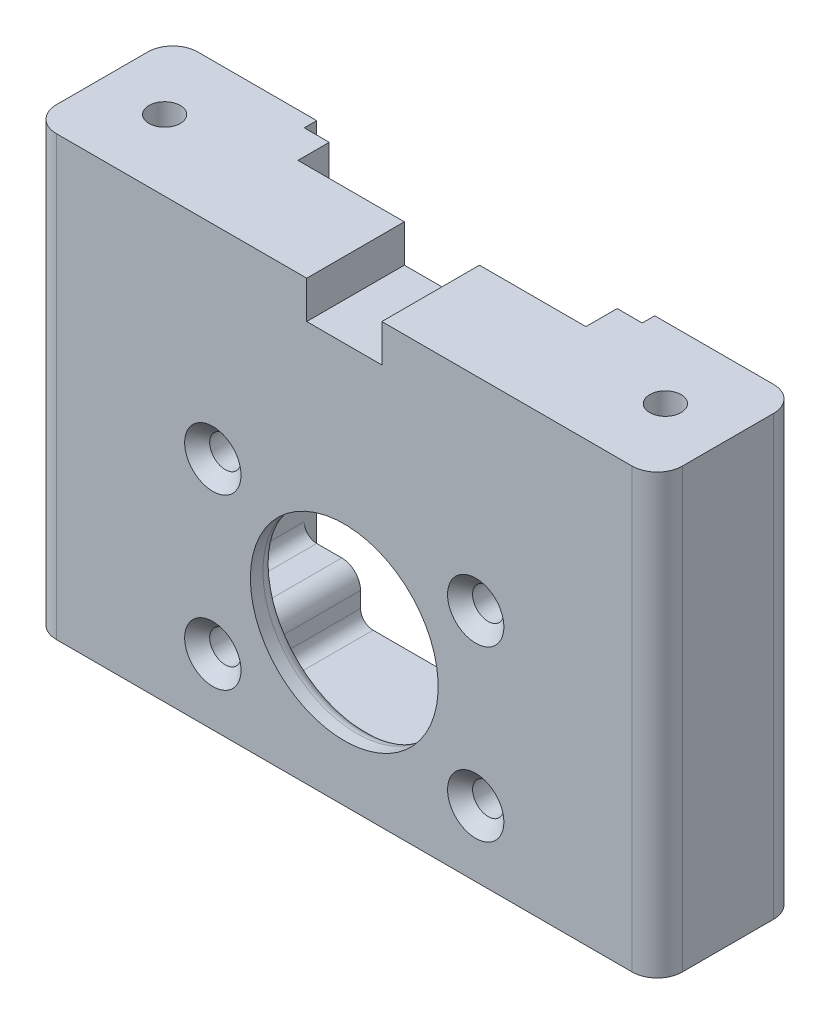
SolidWorks part; units mm, degrees
ref_plane "Спереди" through (0, 0, 0) normal (0, 0, 1) x (1, 0, 0)
ref_plane "Сверху" through (0, 0, 0) normal (0, 1, 0) x (1, 0, 0)
ref_plane "Справа" through (0, 0, 0) normal (1, 0, 0) x (0, 0, -1)
sketch "Эскиз1" plane through (0, 0, 0) normal (0, 0, 1) x (1, 0, 0)
  line L0 (0, 23) -> (0, -12) construction
  line L1 (-25, 23) -> (25, 23)
  line L2 (-25, 23) -> (-25, -12)
  line L3 (-25, -12) -> (25, -12)
  line L4 (25, 23) -> (25, -12)
  line L5 (-25, 0) -> (25, 0) construction
  point P4 (0, 0)
  dimension "D1" = 12
  dimension "D2" = 23
  dimension "D3" = 50
extrude "тело" add sketch "Эскиз1" along normal blind 11.3
sketch "Эскиз2" plane through (0, 0, 0) normal (0, 0, -1) x (-1, 0, 0)
  line L0 (0, 6.75) -> (0, -6.75) construction
  line L1 (-10.5, 6.75) -> (10.5, 6.75) construction
  line L2 (-10.5, 6.75) -> (-10.5, -6.75) construction
  line L3 (-10.5, -6.75) -> (10.5, -6.75) construction
  line L4 (10.5, 6.75) -> (10.5, -6.75) construction
  line L6 (-10.5, 0) -> (10.5, 0) construction
  circle A0 centre (0, 0) radius 7.5
  circle A1 centre (-10.5, 6.75) radius 1.25
  circle A2 centre (10.5, 6.75) radius 1.25
  circle A3 centre (10.5, -6.75) radius 1.25
  circle A4 centre (-10.5, -6.75) radius 1.25
  point P15 (0, 0)
  dimension "D1" = 2.5
  dimension "D4" = 15
  dimension "D2" = 21
  dimension "D3" = 13.5
extrude "отверстия под объектив и крепления" cut sketch "Эскиз2" against normal through all
sketch "Эскиз3" plane through (0, 0, 0) normal (0, 0, -1) x (-1, 0, 0)
  line L1 (-13.5, 10.25) -> (13.5, 10.25)
  line L2 (-13.5, 10.25) -> (-13.5, 8.25)
  line L3 (-9, -9) -> (9, -9)
  line L4 (13.5, 10.25) -> (13.5, 8.25)
  line L5 (-10.5, 8.25) -> (-13.5, 8.25)
  line L6 (-10.5, 5.25) -> (-13.5, 5.25)
  line L7 (10.5, 8.25) -> (13.5, 8.25)
  line L8 (10.5, -5.25) -> (13.5, -5.25)
  line L9 (10.5, 5.25) -> (13.5, 5.25)
  line L10 (-10.5, -5.25) -> (-13.5, -5.25)
  line L11 (-9, -6.75) -> (-9, -9)
  line L12 (-13.5, 5.25) -> (-13.5, -5.25)
  line L13 (9, -6.75) -> (9, -9)
  line L16 (13.5, 5.25) -> (13.5, -5.25)
  arc A0 (-10.5, 5.25) -> (-10.5, 8.25) centre (-10.5, 6.75) ccw
  arc A1 (-9, -6.75) -> (-10.5, -5.25) centre (-10.5, -6.75) ccw
  arc A2 (10.5, 8.25) -> (10.5, 5.25) centre (10.5, 6.75) ccw
  arc A3 (10.5, -5.25) -> (9, -6.75) centre (10.5, -6.75) ccw
  dimension "D2" = 3
  dimension "D1" = 9
  dimension "D3" = 10.25
  dimension "D4" = 13.5
extrude "углубление под выступы камеры" cut sketch "Эскиз3" against normal blind 9.3
sketch "Эскиз4" plane through (0, 0, 0) normal (0, 0, -1) x (-1, 0, 0)
  line L0 (-13.5, 0) -> (13.5, 0) construction
  line L1 (-13.5, 23) -> (13.5, 23)
  line L2 (-13.5, 23) -> (-13.5, -11.5)
  line L3 (-13.5, -11.5) -> (13.5, -11.5)
  line L4 (13.5, 23) -> (13.5, -11.5)
  line L6 (-25, 23) -> (25, 23) construction
  point P6 (0, 0)
  dimension "D1" = 27
  dimension "D2" = 11.5
extrude "углубление под плату камеры" cut sketch "Эскиз4" against normal blind 1
sketch "Эскиз5" plane through (0, 23, 0) normal (0, 1, 0) x (1, 0, 0)
  line L0 (0, 0) -> (0, -11.3) construction
  line L1 (25, -11.3) -> (-25, -11.3) construction
  line L2 (25, 0) -> (13.5, 0) construction
  line L3 (-11.5, 0) -> (11.5, 0)
  line L4 (-11.5, 0) -> (-11.5, -3.5)
  line L5 (-11.5, -3.5) -> (11.5, -3.5)
  line L6 (11.5, 0) -> (11.5, -3.5)
  point P12 (0, 0)
  dimension "D1" = 23
  dimension "D2" = 3.5
extrude "вырез под шлейф" cut sketch "Эскиз5" against normal up to surface (12.75 mm away) up to face at (0, 10.25, 5.15)
fillet "Скругление1" radius 1 2 edges at (0, 10.25, 3.5) (-7.5, 0, 9.3)
fillet "Скругление3" radius 1 26 edges at (-12, 8.25, 9.3) (12, 8.25, 9.3) (13.5, 8.25, 5.15) (13.5, 9.25, 9.3) (0, 10.25, 9.3) (-13.5, 9.25, 9.3) (-13.5, 8.25, 5.15) (-9, 6.75, 9.3) (-12, 5.25, 9.3) (-13.5, 5.25, 5.15) (-13.5, 0, 9.3) (-13.5, -5.25, 5.15) (-12, -5.25, 9.3) (-9.4393, -5.6893, 9.3) (-9, -7.875, 9.3) (-9, -9, 5.15) (0, -9, 9.3) (9, -9, 5.15) (9, -7.875, 9.3) (9.4393, -5.6893, 9.3) (12, -5.25, 9.3) (13.5, -5.25, 5.15) (13.5, 0, 9.3) (12, 5.25, 9.3) (9, 6.75, 9.3) (13.5, 5.25, 5.15)
sketch "Эскиз7" plane through (0, 23, 0) normal (0, 1, 0) x (1, 0, 0)
  line L0 (-25, -5.65) -> (25, -5.65) construction
  line L1 (-25, -11.3) -> (-25, 0) construction
  line L2 (25, -11.3) -> (25, 0) construction
  line L3 (0, -11.3) -> (0, 0) construction
  line L4 (25, -11.3) -> (-25, -11.3) construction
  line L5 (13.5, 0) -> (-13.5, 0) construction
  circle A0 centre (-20, -5.65) radius 1.25
  circle A1 centre (20, -5.65) radius 1.25
  dimension "D1" = 2.5
  dimension "D2" = 40
extrude "отверстия под шурупы" cut sketch "Эскиз7" against normal through all
sketch "Эскиз8" plane through (0, 23, 0) normal (0, 1, 0) x (1, 0, 0)
  line L0 (0, -3.5) -> (0, -11.3) construction
  line L1 (-11.5, -3.5) -> (11.5, -3.5) construction
  line L2 (25, -11.3) -> (-25, -11.3) construction
  line L4 (-3, -11.3) -> (3, -11.3)
  line L5 (-3, -11.3) -> (-3, -3.5)
  line L6 (-3, -3.5) -> (3, -3.5)
  line L7 (3, -11.3) -> (3, -3.5)
  point P10 (0, -3.5)
  dimension "D1" = 6
extrude "паз под стяжку" cut sketch "Эскиз8" against normal blind 3
chamfer "Фаска1" distance 1 angle 45 4 edges at (9.25, -6.75, 11.3) (9.25, 6.75, 11.3) (-11.75, -6.75, 11.3) (-11.75, 6.75, 11.3)
fillet "Скругление2" radius 2 4 edges at (25, 5.5, 0) (25, 5.5, 11.3) (-25, 5.5, 11.3) (-25, 5.5, 0)
